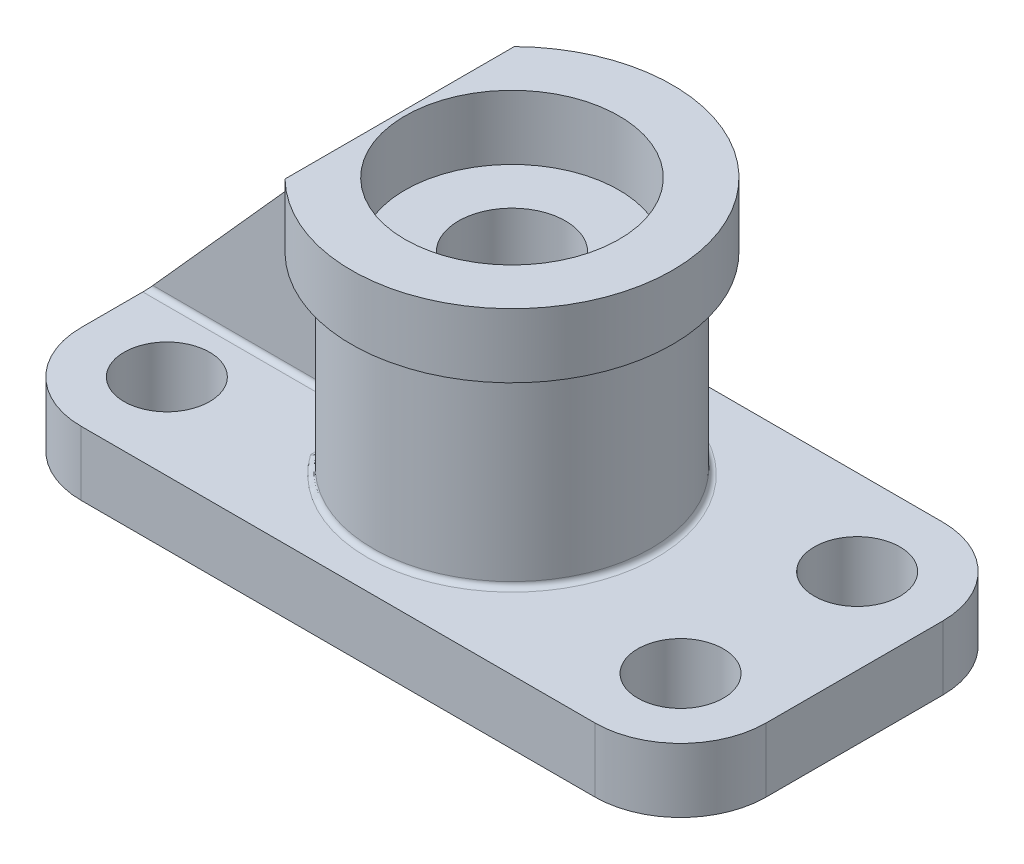
SolidWorks part; units mm, degrees
ref_plane "Ön Düzlem" through (0, 0, 0) normal (0, 0, 1) x (1, 0, 0)
ref_plane "Üst Düzlem" through (0, 0, 0) normal (0, 1, 0) x (1, 0, 0)
ref_plane "Sağ Düzlem" through (0, 0, 0) normal (1, 0, 0) x (0, 0, -1)
sketch "Çizim1" plane through (0, 0, 0) normal (0, 1, 0) x (1, 0, 0)
  line L1 (48, -32.5) -> (-48, -32.5)
  line L2 (64, -16.5) -> (64, 16.5)
  line L3 (48, 32.5) -> (-48, 32.5)
  line L4 (-64, -16.5) -> (-64, 16.5)
  line L5 (64, -32.5) -> (-64, 32.5) construction
  line L6 (64, 32.5) -> (-64, -32.5) construction
  arc A0 (-48, -32.5) -> (-64, -16.5) centre (-48, -16.5) cw
  arc A1 (48, -32.5) -> (64, -16.5) centre (48, -16.5) ccw
  arc A2 (64, 16.5) -> (48, 32.5) centre (48, 16.5) ccw
  arc A3 (-48, 32.5) -> (-64, 16.5) centre (-48, 16.5) ccw
  circle A4 centre (-48, 16.5) radius 8
  circle A5 centre (-48, -16.5) radius 8
  circle A6 centre (48, 16.5) radius 8
  circle A7 centre (48, -16.5) radius 8
  point P0 (0, 0)
  dimension "D3" = 16
  dimension "D4" = 16
  dimension "D5" = 16
  dimension "D6" = 16
  dimension "D7" = 16
  dimension "D1" = 65
  dimension "D2" = 128
extrude "Yükseklik-Ekstrüzyon1" add sketch "Çizim1" along normal blind 12
sketch "Çizim2" plane through (0, 12, 0) normal (0, 1, 0) x (1, 0, 0)
  circle A0 centre (0, 0) radius 26
  circle A1 centre (0, 0) radius 10
extrude "Yükseklik-Ekstrüzyon2" add sketch "Çizim2" along normal blind 36
sketch "Çizim3" plane through (0, 48, 0) normal (0, 1, 0) x (1, 0, 0)
  circle A0 centre (0, 0) radius 10
extrude "Kes-Ekstrüzyon1" cut sketch "Çizim3" against normal through all
sketch "Çizim4" plane through (0, 48, 0) normal (0, 1, 0) x (1, 0, 0)
  circle A0 centre (0, 0) radius 30
  circle A1 centre (0, 0) radius 20
extrude "Yükseklik-Ekstrüzyon3" add sketch "Çizim4" along normal blind 12
sketch "Çizim8" plane through (0, 60, 0) normal (0, 1, 0) x (1, 0, 0)
  line L1 (-36.018, 28.0544) -> (-21, 28.0544)
  line L2 (-36.018, 28.0544) -> (-36.018, -30.766)
  line L3 (-36.018, -30.766) -> (-21, -30.766)
  line L4 (-21, 28.0544) -> (-21, -30.766)
  dimension "D1" = 21
extrude "Kes-Ekstrüzyon5" cut sketch "Çizim8" against normal up to surface (48 mm away) up to face at (0, 12, -26)
sketch "Çizim9" plane through (0, 0, 0) normal (0, 0, 1) x (1, 0, 0)
  line L0 (-21, 60) -> (-64, 12)
rib "Feder1" sketch "Çizim9" sketch "Çizim9" thickness 8 extrusion direction parallel to sketch draft on no parameters "D1"=8
fillet "Radyus1" radius 1 7 edges at (-21, 36, -4) (-21, 12, -9.6649) (-42.5, 12, -4) (-42.5, 12, 4) (-21, 12, 9.6649) (26, 12, 0) (-21, 36, 4)
